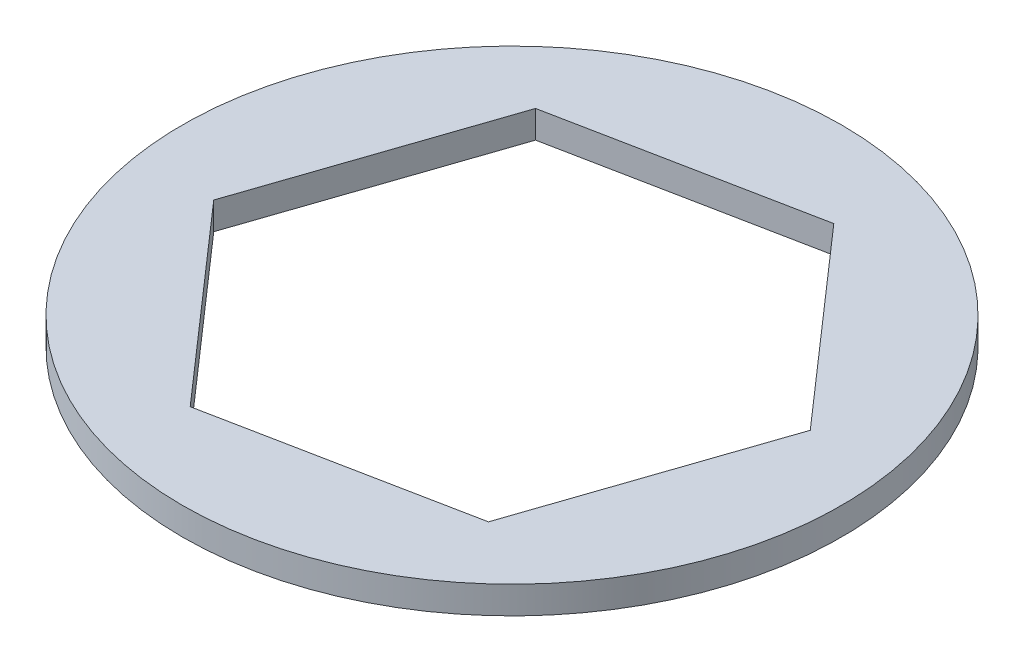
SolidWorks part; units mm, degrees
material "PET"
ref_plane "Front Plane" through (0, 0, 0) normal (0, 0, 1) x (1, 0, 0)
ref_plane "Top Plane" through (0, 0, 0) normal (0, 1, 0) x (1, 0, 0)
ref_plane "Right Plane" through (0, 0, 0) normal (1, 0, 0) x (0, 0, -1)
sketch "Sketch1" plane through (0, 0, 0) normal (0, 1, 0) x (1, 0, 0)
  line L1 (2.3586, 6.9426) -> (-4.8332, 5.5139)
  line L2 (-4.8332, 5.5139) -> (-7.1918, -1.4287)
  line L3 (-7.1918, -1.4287) -> (-2.3586, -6.9426)
  line L4 (-2.3586, -6.9426) -> (4.8332, -5.5139)
  line L5 (4.8332, -5.5139) -> (7.1918, 1.4287)
  line L6 (7.1918, 1.4287) -> (2.3586, 6.9426)
  circle A0 centre (0, 0) radius 9.525
  circle A2 centre (0, 0) radius 6.35 construction
  dimension "D1" = 12.7
  dimension "D2" = 19.05
extrude "Boss-Extrude1" add sketch "Sketch1" along normal blind 0.7937
